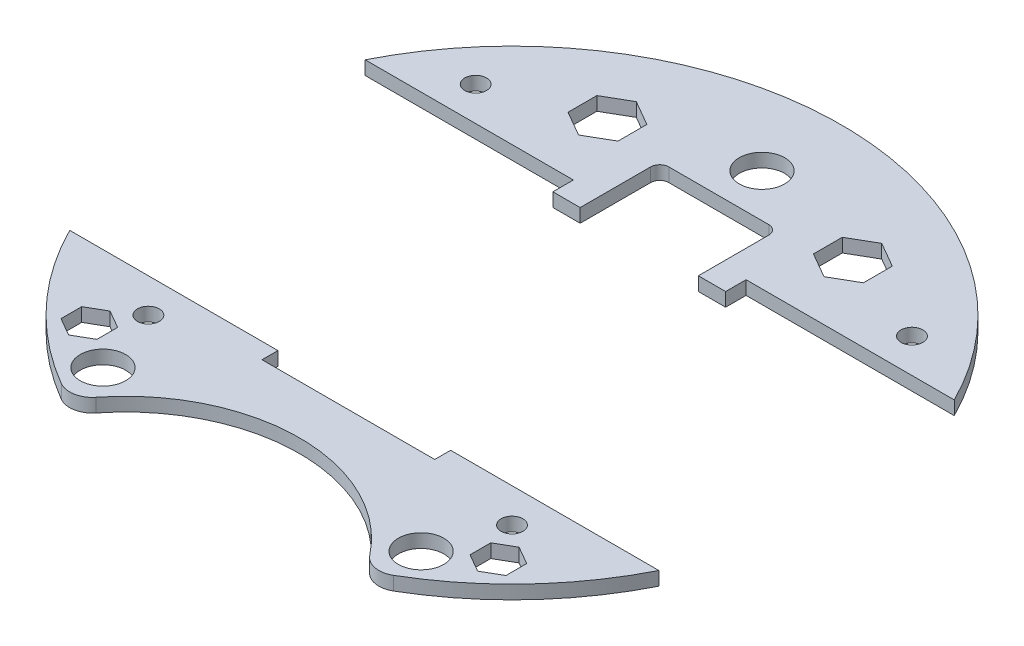
SolidWorks part; units mm, degrees
material "Acrylic (Medium-high impact)"
ref_plane "Front Plane" through (0, 0, 0) normal (0, 0, 1) x (1, 0, 0)
ref_plane "Top Plane" through (0, 0, 0) normal (0, 1, 0) x (1, 0, 0)
ref_plane "Right Plane" through (0, 0, 0) normal (1, 0, 0) x (0, 0, -1)
sketch "Sketch1" plane through (0, 0, 0) normal (0, 1, 0) x (1, 0, 0)
  line L0 (0, -85) -> (-32.4891, -64.8129) construction
  line L1 (0, -85) -> (0, 0) construction
  arc A0 (36.5434, -62.6165) -> (-36.5434, -62.6165) centre (0, 0) ccw
  arc A1 (30.0898, -61.3851) -> (-30.0898, -61.3851) centre (0, -85) ccw
  arc A2 (36.5434, -62.6165) -> (30.0898, -61.3851) centre (34.0231, -58.2982) cw
  arc A3 (-30.0898, -61.3851) -> (-36.5434, -62.6165) centre (-34.0231, -58.2982) cw
  dimension "D1" = 145
  dimension "D2" = 76.5
  dimension "D4" = 5
  dimension "D3" = 85
extrude "Boss-Extrude1" add sketch "Sketch1" along normal blind 3
sketch "solenoid placement" plane through (0, 3, 0) normal (0, 1, 0) x (1, 0, 0)
  line L4 (-19, -36) -> (19, -36)
  line L5 (-19, 28) -> (-19, -36)
  line L6 (19, 28) -> (-19, 28)
  line L7 (19, -36) -> (19, 28)
  line L8 (-19, -36) -> (19, -36)
  line L9 (-19, 28) -> (-19, -36)
  line L10 (19, 28) -> (-19, 28)
  line L11 (19, -36) -> (19, 28)
  dimension "D1" = 0
extrude "Cut-Extrude1" cut sketch "solenoid placement" against normal through all
sketch "Sketch5" plane through (0, 3, 0) normal (0, 1, 0) x (1, 0, 0)
  line L12 (-21.5, 51.1754) -> (-27, 54.3509)
  line L13 (-27, 54.3509) -> (-32.5, 51.1754)
  line L14 (-32.5, 51.1754) -> (-32.5, 44.8246)
  line L15 (-32.5, 44.8246) -> (-27, 41.6491)
  line L16 (-27, 41.6491) -> (-21.5, 44.8246)
  line L17 (-21.5, 44.8246) -> (-21.5, 51.1754)
  line L18 (-21.5, 51.1754) -> (-27, 54.3509)
  line L19 (-27, 54.3509) -> (-32.5, 51.1754)
  line L20 (-32.5, 51.1754) -> (-32.5, 44.8246)
  line L21 (-32.5, 44.8246) -> (-27, 41.6491)
  line L22 (-27, 41.6491) -> (-21.5, 44.8246)
  line L23 (-21.5, 44.8246) -> (-21.5, 51.1754)
  line L24 (21.5, 51.1754) -> (21.5, 44.8246)
  line L25 (21.5, 44.8246) -> (27, 41.6491)
  line L26 (27, 41.6491) -> (32.5, 44.8246)
  line L27 (32.5, 44.8246) -> (32.5, 51.1754)
  line L28 (32.5, 51.1754) -> (27, 54.3509)
  line L29 (27, 54.3509) -> (21.5, 51.1754)
  line L30 (21.5, 51.1754) -> (21.5, 44.8246)
  line L31 (21.5, 44.8246) -> (27, 41.6491)
  line L32 (27, 41.6491) -> (32.5, 44.8246)
  line L33 (32.5, 44.8246) -> (32.5, 51.1754)
  line L34 (32.5, 51.1754) -> (27, 54.3509)
  line L35 (27, 54.3509) -> (21.5, 51.1754)
  dimension "D1" = 0
  dimension "D2" = 0
extrude "Cut-Extrude5" cut sketch "Sketch5" against normal through all
sketch "Sketch6" plane through (0, 3, 0) normal (0, 1, 0) x (1, 0, 0)
  circle A1 centre (40, -40) radius 2.4
  circle A2 centre (40, -40) radius 2.4
  circle A3 centre (-40, -40) radius 2.4
  circle A4 centre (-40, -40) radius 2.4
  circle A5 centre (48, 40) radius 2.4
  circle A6 centre (48, 40) radius 2.4
  circle A7 centre (-48, 40) radius 2.4
  circle A8 centre (-48, 40) radius 2.4
  dimension "D1" = 0
  dimension "D2" = 0
  dimension "D3" = 0
  dimension "D4" = 0
extrude "Cut-Extrude6" cut sketch "Sketch6" against normal through all
sketch "Sketch3" plane through (0, 3, 0) normal (0, 1, 0) x (1, 0, 0)
  line L0 (-19, 28) -> (-19, 32.5)
  line L1 (72.5, -32.5) -> (-72.5, -32.5)
  line L2 (72.5, -32.5) -> (72.5, 32.5)
  line L3 (72.5, 32.5) -> (19, 32.5)
  line L4 (-72.5, -32.5) -> (-72.5, 32.5)
  line L5 (72.5, -32.5) -> (-72.5, 32.5) construction
  line L6 (72.5, 32.5) -> (-72.5, -32.5) construction
  line L7 (-19, 28) -> (19, 28)
  line L8 (19, 28) -> (19, 32.5)
  line L9 (-19, 32.5) -> (-72.5, 32.5)
  arc A0 (36.5434, -62.6165) -> (-36.5434, -62.6165) centre (0, 0) ccw construction
  point P0 (0, 0)
  dimension "D1" = 65
extrude "Cut-Extrude3" cut sketch "Sketch3" against normal through all
sketch "Sketch7" plane through (0, 3, 0) normal (0, 1, 0) x (1, 0, 0)
  line L8 (13, 28) -> (13, 43.5)
  line L9 (-13, 28) -> (13, 28)
  line L10 (-13, 43.5) -> (-13, 28)
  line L11 (11, 45.5) -> (-11, 45.5)
  line L20 (13, 28) -> (13, 43.5)
  line L21 (-13, 28) -> (13, 28)
  line L22 (-13, 43.5) -> (-13, 28)
  line L23 (11, 45.5) -> (-11, 45.5)
  arc A4 (-11, 45.5) -> (-13, 43.5) centre (-11, 43.5) ccw
  arc A5 (13, 43.5) -> (11, 45.5) centre (11, 43.5) ccw
  arc A10 (-11, 45.5) -> (-13, 43.5) centre (-11, 43.5) ccw
  arc A11 (13, 43.5) -> (11, 45.5) centre (11, 43.5) ccw
  dimension "D1" = 0
extrude "Cut-Extrude7" cut sketch "Sketch7" against normal through all
sketch "Sketch8" plane through (0, 3, 0) normal (0, -1, 0) x (1, 0, 0)
  circle A1 centre (35, 55) radius 5
  circle A2 centre (35, 55) radius 5
  circle A3 centre (-35, 55) radius 5
  circle A4 centre (-35, 55) radius 5
  dimension "D1" = 0
  dimension "D2" = 0
extrude "Cut-Extrude9" cut sketch "Sketch8" along normal through all
sketch "Sketch9" plane through (0, 3, 0) normal (0, -1, 0) x (1, 0, 0)
  circle A1 centre (0, -55) radius 5
  circle A2 centre (0, -55) radius 5
  dimension "D1" = 0
extrude "Cut-Extrude11" cut sketch "Sketch9" along normal through all
sketch "Sketch10" plane through (0, 3, 0) normal (0, 1, 0) x (1, 0, 0)
  line L0 (0, 0) -> (0, -22.8708) construction
  line L1 (48.95, -45.7195) -> (45, -43.4389)
  line L2 (45, -43.4389) -> (41.05, -45.7195)
  line L3 (41.05, -45.7195) -> (41.05, -50.2805)
  line L4 (41.05, -50.2805) -> (45, -52.5611)
  line L5 (45, -52.5611) -> (48.95, -50.2805)
  line L6 (48.95, -50.2805) -> (48.95, -45.7195)
  line L7 (-48.95, -50.2805) -> (-48.95, -45.7195)
  line L8 (-45, -52.5611) -> (-48.95, -50.2805)
  line L9 (-41.05, -50.2805) -> (-45, -52.5611)
  line L10 (-41.05, -45.7195) -> (-41.05, -50.2805)
  line L11 (-45, -43.4389) -> (-41.05, -45.7195)
  line L12 (-48.95, -45.7195) -> (-45, -43.4389)
  circle A0 centre (45, -48) radius 3.95 construction
  circle A1 centre (-45, -48) radius 3.95 construction
  dimension "D1" = 7.9
  dimension "D2" = 45
  dimension "D3" = 48
extrude "Cut-Extrude12" cut sketch "Sketch10" against normal through all
equation "\"smallPulleyTeeth\"= 30"
equation "\"largePulleyTeeth\"= 30"
equation "\"eighthThick\"= 3.0mm"
equation "\"sixteenthThick\" = 1.7mm"
equation "\"quarterThick\"=6.0mm"
equation "\"OD\" = 145mm"
equation "\"puckAngle\" = 60.5deg"
equation "\"D1@Sketch1\"=\"OD\""
equation "\"puckDiam\" = 76.5mm"
equation "\"D2@Sketch1\"=\"puckDiam\""
equation "\"D1@Boss-Extrude1\"=\"eighthThick\""
equation "\"axlePress\" = 5.9mm"
equation "\"press\" = 0.2mm"
equation "\"wheelClear\" = 0.3mm"
equation "\"10-32clear\" = 4.8mm"
equation "\"6-32clear\" = 3.3mm"
equation "\"8-32clear\" = 4.0mm"
equation "\"wheelHeight\" = 22mm"
equation "\"wheelWell\" = 65mm"
equation "\"D1@Sketch3\"=\"wheelWell\""
equation "\"puckDist\" = 85mm"
equation "\"scoopFillet\" = 5mm"
equation "\"4-40clear\" = 3.0mm"
equation "\"D3@Sketch1\"=\"puckDist\""
equation "\"D4@Sketch1\"=\"scoopFillet\""
